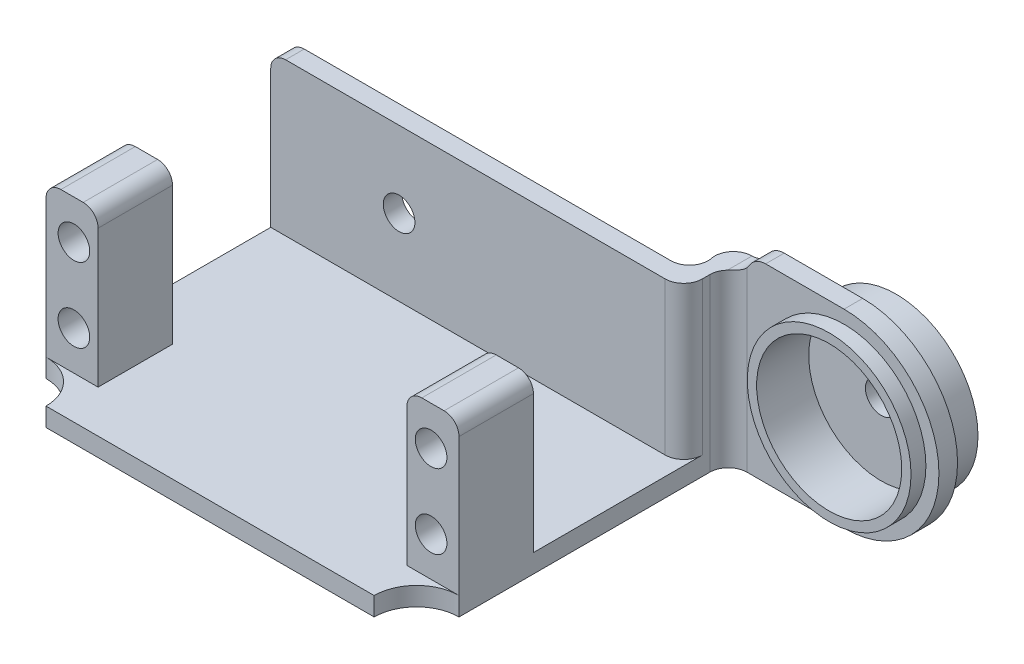
SolidWorks part; units mm, degrees
ref_plane "Front" through (0, 0, 0) normal (0, 0, 1) x (1, 0, 0)
ref_plane "Top" through (0, 0, 0) normal (0, 1, 0) x (1, 0, 0)
ref_plane "Right" through (0, 0, 0) normal (1, 0, 0) x (0, 0, -1)
sketch "Sketch1" plane through (0, 0, 0) normal (0, 1, 0) x (1, 0, 0)
  line L1 (0, 0) -> (55.5, 0)
  line L2 (0, 0) -> (0, 35.9)
  line L3 (0, 35.9) -> (55.5, 35.9)
  line L4 (55.5, 0) -> (55.5, 35.9)
  dimension "D1" = 35.9
  dimension "D2" = 55.5
extrude "bracketBase" add sketch "Sketch1" along normal blind 2.5
ref_plane "referencePlane1" through (0, 0, -8.2) normal (0, 0, 1) x (1, 0, 0)
sketch "Sketch2" plane through (0, 0, -8.2) normal (0, 0, 1) x (1, 0, 0)
  line L0 (27.75, 2.5) -> (27.75, 23) construction
  line L1 (0, 2.5) -> (7, 2.5)
  line L2 (0, 2.5) -> (0, 23)
  line L3 (0, 23) -> (7, 23)
  line L4 (7, 2.5) -> (7, 23)
  line L5 (0, 2.5) -> (55.5, 2.5) construction
  line L6 (55.5, 23) -> (48.5, 23)
  line L7 (48.5, 2.5) -> (48.5, 23)
  line L8 (55.5, 2.5) -> (48.5, 2.5)
  line L9 (55.5, 2.5) -> (55.5, 23)
  dimension "D1" = 20.5
  dimension "D2" = 7
extrude "servoMountingHoleTabs" add sketch "Sketch2" along normal blind 2.5
sketch "Sketch3" plane through (0, 0, -5.7) normal (0, 0, 1) x (1, 0, 0)
  line L0 (0, 12.75) -> (7, 12.75) construction
  line L3 (0, 23) -> (0, 2.5) construction
  line L4 (7, 2.5) -> (7, 23) construction
  line L5 (7, 23) -> (0, 23) construction
  line L6 (27.75, 2.5) -> (27.75, 23) construction
  line L7 (0, 2.5) -> (55.5, 2.5) construction
  circle A0 centre (3.75, 17.75) radius 2.125
  circle A1 centre (3.75, 7.75) radius 2.125
  circle A2 centre (51.75, 7.75) radius 2.125
  circle A3 centre (51.75, 17.75) radius 2.125
  dimension "D1" = 4.25
  dimension "D2" = 3.75
  dimension "D3" = 5.25
extrude "servoMountingHoles" cut sketch "Sketch3" against normal blind 2.5
sketch "Sketch4" plane through (0, 0, 0) normal (0, 1, 0) x (1, 0, 0)
  line L0 (55.5, 8.2) -> (55.5, 35.9) construction
  line L1 (0, 35.9) -> (55.5, 35.9)
  line L2 (0, 35.9) -> (0, 38.4)
  line L3 (0, 38.4) -> (55.5, 38.4)
  line L4 (55.5, 35.9) -> (55.5, 38.4)
  dimension "D1" = 2.5
extrude "baseWall" add sketch "Sketch4" along normal up to surface (23 mm away) up to face at (3.5, 23, -6.95)
sketch "Sketch6" plane through (0, 2.5, 0) normal (0, 1, 0) x (1, 0, 0)
  circle A0 centre (0, 0) radius 5.7
  circle A1 centre (55.5, 0) radius 5.7
extrude "baseTrim" cut sketch "Sketch6" against normal blind 2.5
fillet "Fillet1" radius 2 6 edges at (7, 23, -6.95) (48.5, 23, -6.95) (0, 23, -6.95) (55.5, 23, -6.95) (55.5, 23, -37.15) (0, 23, -37.15)
sketch "Sketch7" plane through (0, 0, -38.4) normal (0, 0, -1) x (-1, 0, 0)
  line L0 (0, 21) -> (0, 0) construction
  line L1 (-55.5, 0) -> (0, 0) construction
  circle A0 centre (-17.25, 12.75) radius 2.125
  dimension "D1" = 4.25
  dimension "D2" = 17.25
  dimension "D3" = 12.75
extrude "M4mountingHole" cut sketch "Sketch7" against normal blind 10
sketch "Sketch8" plane through (0, 0, -8.2) normal (0, 0, -1) x (-1, 0, 0)
  line L4 (-48.5, 2.5) -> (-48.5, 21)
  line L5 (-50.5, 23) -> (-53.5, 23)
  line L6 (-55.5, 21) -> (-55.5, 2.5)
  line L7 (-55.5, 2.5) -> (-48.5, 2.5)
  line L8 (-48.5, 2.5) -> (-48.5, 21)
  line L9 (-50.5, 23) -> (-53.5, 23)
  line L10 (-55.5, 21) -> (-55.5, 2.5)
  line L11 (-55.5, 2.5) -> (-48.5, 2.5)
  line L12 (-2, 23) -> (-5, 23)
  line L13 (-7, 21) -> (-7, 2.5)
  line L14 (-7, 2.5) -> (0, 2.5)
  line L15 (0, 2.5) -> (0, 21)
  line L16 (-2, 23) -> (-5, 23)
  line L17 (-7, 21) -> (-7, 2.5)
  line L18 (-7, 2.5) -> (0, 2.5)
  line L19 (0, 2.5) -> (0, 21)
  circle A0 centre (-51.75, 17.75) radius 2.125 construction
  circle A1 centre (-51.75, 17.75) radius 2.125
  arc A2 (-48.5, 21) -> (-50.5, 23) centre (-50.5, 21) ccw
  arc A3 (-53.5, 23) -> (-55.5, 21) centre (-53.5, 21) ccw
  arc A4 (-48.5, 21) -> (-50.5, 23) centre (-50.5, 21) ccw
  arc A5 (-53.5, 23) -> (-55.5, 21) centre (-53.5, 21) ccw
  arc A6 (-5, 23) -> (-7, 21) centre (-5, 21) ccw
  arc A7 (0, 21) -> (-2, 23) centre (-2, 21) ccw
  arc A8 (-5, 23) -> (-7, 21) centre (-5, 21) ccw
  arc A9 (0, 21) -> (-2, 23) centre (-2, 21) ccw
  circle A10 centre (-51.75, 7.75) radius 2.125 construction
  circle A11 centre (-51.75, 7.75) radius 2.125
  circle A12 centre (-3.75, 17.75) radius 2.125 construction
  circle A13 centre (-3.75, 17.75) radius 2.125
  circle A14 centre (-3.75, 7.75) radius 2.125 construction
  circle A15 centre (-3.75, 7.75) radius 2.125
  dimension "D1" = 0
  dimension "D2" = 0
extrude "tabExtension" add sketch "Sketch8" along normal blind 7.5
sketch "Sketch10" plane through (0, 0, 0) normal (0, -1, 0) x (1, 0, 0)
  line L0 (86.5796, -41.8997) -> (55.5, -41.8997)
  line L1 (86.5796, -44.3997) -> (47.5, -44.3997)
  line L2 (86.5796, -41.8997) -> (86.5796, -44.3997)
  line L3 (2, -38.4) -> (53.5, -38.4) construction
  line L4 (55.5, -38.4) -> (55.5, -35.9)
  line L5 (55.5, -41.8997) -> (55.5, -38.4)
  line L7 (47.5, -38.4) -> (47.5, -44.3997)
  line L8 (55.5, -5.7) -> (55.5, -38.4) construction
  line L9 (55.5, -35.9) -> (47.5, -35.9)
  line L10 (47.5, -35.9) -> (47.5, -38.4)
  line L11 (55.5, -35.9) -> (0, -35.9) construction
  dimension "D1" = 31.0796
  dimension "D2" = 39.0796
  dimension "D3" = 2.5
  dimension "D4" = 3.4997
extrude "Boss-Extrude1" add sketch "Sketch10" against normal blind 25.5
ref_plane "Plane1" through (0, 0, -39.8997) normal (0, 0, 1) x (1, 0, 0)
sketch "Sketch12" plane through (0, 0, -39.8997) normal (0, 0, 1) x (1, 0, 0)
  line L0 (55.5, 2.5) -> (55.5, 21) construction
  circle A0 centre (71.0398, 12.75) radius 11
  dimension "D1" = 22
  dimension "D2" = 12.75
  dimension "D3" = 15.5398
extrude "Boss-Extrude2" add sketch "Sketch12" against normal blind 9
sketch "Sketch13" plane through (0, 0, -39.8997) normal (0, 0, 1) x (1, 0, 0)
  circle A0 centre (71.0398, 12.75) radius 9.75
  dimension "D1" = 19.5
extrude "Cut-Extrude1" cut sketch "Sketch13" against normal offset from surface (7 mm away) 2 up to face at (82.0398, 12.75, -48.8997)
sketch "Sketch14" plane through (0, 0, -46.8997) normal (0, 0, 1) x (1, 0, 0)
  circle A0 centre (71.0398, 12.75) radius 2.125
  dimension "D1" = 4.25
extrude "Cut-Extrude2" cut sketch "Sketch14" against normal blind 2
sketch "Sketch15" plane through (47.5, 0, 0) normal (-1, 0, 0) x (0, 0, 1)
  line L0 (-44.3997, 25.5) -> (-44.3997, 0) construction
  line L1 (-35.9, 25.5) -> (-44.3997, 25.5)
  line L2 (-35.9, 25.5) -> (-35.9, 23)
  line L3 (-35.9, 23) -> (-44.3997, 23)
  line L4 (-44.3997, 25.5) -> (-44.3997, 23)
  line L5 (-35.9, 23) -> (-38.4, 23) construction
extrude "Cut-Extrude3" cut sketch "Sketch15" against normal up to surface (8 mm away) up to face at (55.5, 11.1667, -22.6777)
fillet "Fillet2" radius 2.5 2 edges at (47.5, 11.5, -44.3997) (55.5, 12.75, -35.9)
fillet "Fillet4" radius 2.5 2 edges at (55.5, 11.5, -41.8997) (47.5, 11.5, -38.4)
sketch "Sketch16" plane through (0, 0, -41.8997) normal (0, 0, 1) x (1, 0, 0)
  line L0 (86.5796, 25.5) -> (55.5, 25.5) construction
  line L1 (60.5, 25.5) -> (55.5, 25.5)
  line L2 (55.5, 25.5) -> (55.5, 23)
  line L3 (55.5, 23) -> (58, 23)
  arc A0 (58, 23) -> (60.5, 25.5) centre (60.5, 23) cw
extrude "Cut-Extrude4" cut sketch "Sketch16" against normal through all
fillet "Fillet5" radius 2.5 1 edges at (58, 23, -43.1497)
sketch "Sketch17" plane through (0, 0, -41.8997) normal (0, 0, 1) x (1, 0, 0)
  line L0 (71.0398, 0) -> (86.5796, 0)
  line L1 (86.5796, 0) -> (86.5796, 25.5)
  line L2 (86.5796, 25.5) -> (71.0398, 25.5)
  arc A0 (71.0398, 0) -> (71.0398, 25.5) centre (71.0398, 12.75) ccw
extrude "Cut-Extrude5" cut sketch "Sketch17" against normal blind 25
sketch "Sketch18" plane through (0, 23, 0) normal (0, 1, 0) x (1, 0, 0)
  line L0 (45, 38.4) -> (51.2708, 38.4)
  line L1 (56.1699, 44.3997) -> (50, 44.3997) construction
  line L2 (47.5, 41.8997) -> (47.5, 40.9) construction
  line L3 (47.5, 41.8997) -> (47.5, 40.9)
  line L4 (56.1699, 44.3997) -> (50, 44.3997)
  arc A0 (56.1699, 44.3997) -> (53.7204, 41.3998) centre (56.1699, 41.8997) ccw
  arc A1 (53.7204, 41.3998) -> (51.2708, 38.4) centre (51.2708, 40.9) cw
  arc A2 (45, 38.4) -> (47.5, 40.9) centre (45, 40.9) ccw construction
  arc A3 (45, 38.4) -> (47.5, 40.9) centre (45, 40.9) ccw
  arc A4 (50, 44.3997) -> (47.5, 41.8997) centre (50, 41.8997) ccw construction
  arc A5 (50, 44.3997) -> (47.5, 41.8997) centre (50, 41.8997) ccw
  dimension "D1" = 2.5
  dimension "D2" = 2.5
extrude "Cut-Extrude6" cut sketch "Sketch18" against normal through all body kept at (55.5, 23, -39.3997)
ref_plane "Plane2" through (0, 0, 0) normal (0, 0, 1) x (1, 0, 0)
mirror "Mirror1" about plane through (0, 0, 0) normal (0, 0, 1) of bodies 118
sketch "Sketch19" plane through (0, 0, 0) normal (0, 0, 1) x (1, 0, 0)
  line L1 (-73.8417, 72.2477) -> (103.3977, 72.2477)
  line L2 (-73.8417, 72.2477) -> (-73.8417, -56.9909)
  line L3 (-73.8417, -56.9909) -> (103.3977, -56.9909)
  line L4 (103.3977, 72.2477) -> (103.3977, -56.9909)
extrude "Cut-Extrude7" cut sketch "Sketch19" along normal blind 81
